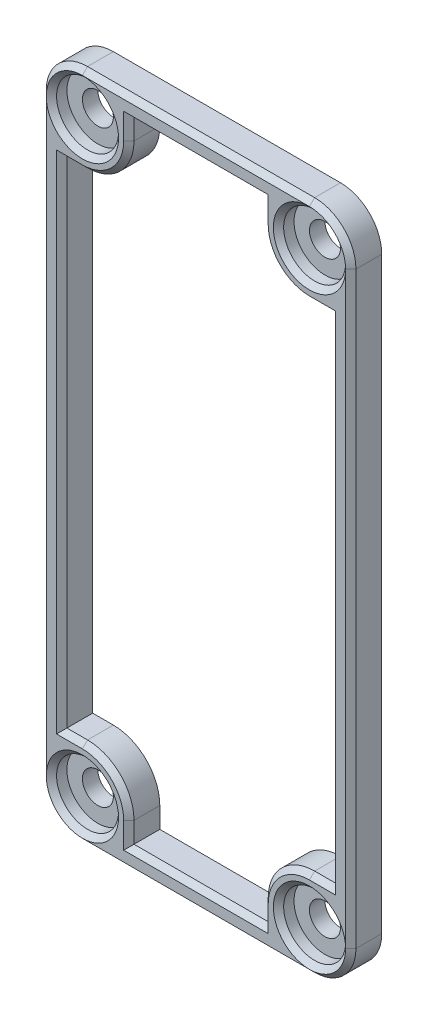
SolidWorks part; units mm, degrees
ref_plane "Front Plane" through (0, 0, 0) normal (0, 0, 1) x (1, 0, 0)
ref_plane "Top Plane" through (0, 0, 0) normal (0, 1, 0) x (1, 0, 0)
ref_plane "Right Plane" through (0, 0, 0) normal (1, 0, 0) x (0, 0, -1)
sketch "Sketch1" plane through (0, 0, 0) normal (0, 0, 1) x (1, 0, 0)
  line L1 (11, -32.5) -> (-11, -32.5)
  line L2 (15, -28.5) -> (15, 28.5)
  line L3 (11, 32.5) -> (-11, 32.5)
  line L4 (-15, -28.5) -> (-15, 28.5)
  line L5 (15, -32.5) -> (-15, 32.5) construction
  line L6 (15, 32.5) -> (-15, -32.5) construction
  arc A0 (11, -32.5) -> (15, -28.5) centre (11, -28.5) ccw
  arc A1 (-11, -32.5) -> (-15, -28.5) centre (-11, -28.5) cw
  arc A2 (15, 28.5) -> (11, 32.5) centre (11, 28.5) ccw
  arc A3 (-11, 32.5) -> (-15, 28.5) centre (-11, 28.5) ccw
  point P0 (0, 0)
  dimension "D3" = 4
  dimension "D1" = 30
  dimension "D2" = 65
extrude "Base" add sketch "Sketch1" along normal blind 3
sketch "Sketch2" plane through (0, 0, 3) normal (0, 0, 1) x (1, 0, 0)
  line L1 (11, -28.5) -> (-11, -28.5) construction
  line L2 (11, -28.5) -> (11, 28.5) construction
  line L3 (11, 28.5) -> (-11, 28.5) construction
  line L4 (-11, -28.5) -> (-11, 28.5) construction
  line L5 (11, -28.5) -> (-11, 28.5) construction
  line L6 (11, 28.5) -> (-11, -28.5) construction
  circle A0 centre (-11, 28.5) radius 1.5
  circle A1 centre (-11, -28.5) radius 1.5
  circle A2 centre (11, -28.5) radius 1.5
  circle A3 centre (11, 28.5) radius 1.5
  point P0 (0, 0)
  dimension "D1" = 3
  dimension "D2" = 22
  dimension "D3" = 57
extrude "Cut-Extrude1" cut sketch "Sketch2" against normal through all
sketch "Sketch3" plane through (0, 0, 3) normal (0, 0, 1) x (1, 0, 0)
  line L0 (6.5, 28.5) -> (6.5, 30.5)
  line L1 (-6.5, 28.5) -> (-6.5, 30.5)
  line L2 (11, 24) -> (13, 24)
  line L3 (-11, 24) -> (-13, 24)
  line L4 (-6.5, -28.5) -> (-6.5, -30.5)
  line L5 (6.5, -28.5) -> (6.5, -30.5)
  line L6 (11, -24) -> (13, -24)
  line L7 (-11, -24) -> (-13, -24)
  line L8 (15, -28.5) -> (15, 28.5) construction
  line L14 (13, -24) -> (13, 24)
  line L16 (-13, 28.5) -> (-13, -28.5)
  line L17 (-13, 24) -> (-13, -24)
  line L19 (11, 30.5) -> (-11, 30.5)
  line L20 (6.5, 30.5) -> (-6.5, 30.5)
  line L22 (-11, -30.5) -> (11, -30.5)
  line L23 (-6.5, -30.5) -> (6.5, -30.5)
  arc A0 (-11, 24) -> (-6.5, 28.5) centre (-11, 28.5) ccw
  arc A1 (6.5, 28.5) -> (11, 24) centre (11, 28.5) ccw
  arc A2 (-6.5, -28.5) -> (-11, -24) centre (-11, -28.5) ccw
  arc A3 (11, -24) -> (6.5, -28.5) centre (11, -28.5) ccw
  circle A19 centre (11, 28.5) radius 1.5 construction
  circle A20 centre (-11, -28.5) radius 1.5 construction
  circle A30 centre (11, -28.5) radius 1.5 construction
  circle A31 centre (-11, 28.5) radius 1.5 construction
  dimension "D15" = 4.5
  dimension "D2" = 2
  dimension "D4" = 2
  dimension "D5" = 2
  dimension "D6" = 2
extrude "Cut-Extrude2" cut sketch "Sketch3" against normal through all contours L17 | L17 A2 | A2 L23 A3 | A3 L14 | L14 | L14 | L14 A1 | A1 L20 A0 | L17 | A0 L17 region at (0, 0, 3)
sketch "Sketch6" plane through (0, 0, 3) normal (0, 0, 1) x (1, 0, 0)
  circle A0 centre (-11, -28.5) radius 3
  circle A1 centre (11, -28.5) radius 3
  circle A2 centre (11, 28.5) radius 3
  circle A3 centre (-11, 28.5) radius 3
  dimension "D1" = 6
extrude "Cut-Extrude3" cut sketch "Sketch6" against normal blind 1.5
chamfer "Chamfer2" distance 0.5 angle 45 28 edges at (7.818, -25.318, 3) (-7.818, -25.318, 3) (-7.818, 25.318, 3) (7.818, 25.318, 3) (0, -32.5, 3) (-13.8284, -31.3284, 3) (-15, 0, 3) (-13.8284, 31.3284, 3) (0, 32.5, 3) (13.8284, 31.3284, 3) (15, 0, 3) (13.8284, -31.3284, 3) (-8, -28.5, 3) (-8, 28.5, 3) (14, 28.5, 3) (14, -28.5, 3) (13, 0, 3) (0, -30.5, 3) (0, 30.5, 3) (-13, 0, 3) (12, 24, 3) (6.5, 29.5, 3) (-6.5, 29.5, 3) (-12, 24, 3) (-12, -24, 3) (-6.5, -29.5, 3) (6.5, -29.5, 3) (12, -24, 3)
equation "\"D3@Sketch2\"=\"D2@Sketch1\"-8"
equation "\"D2@Sketch3\"=\"D4@Sketch3\""
